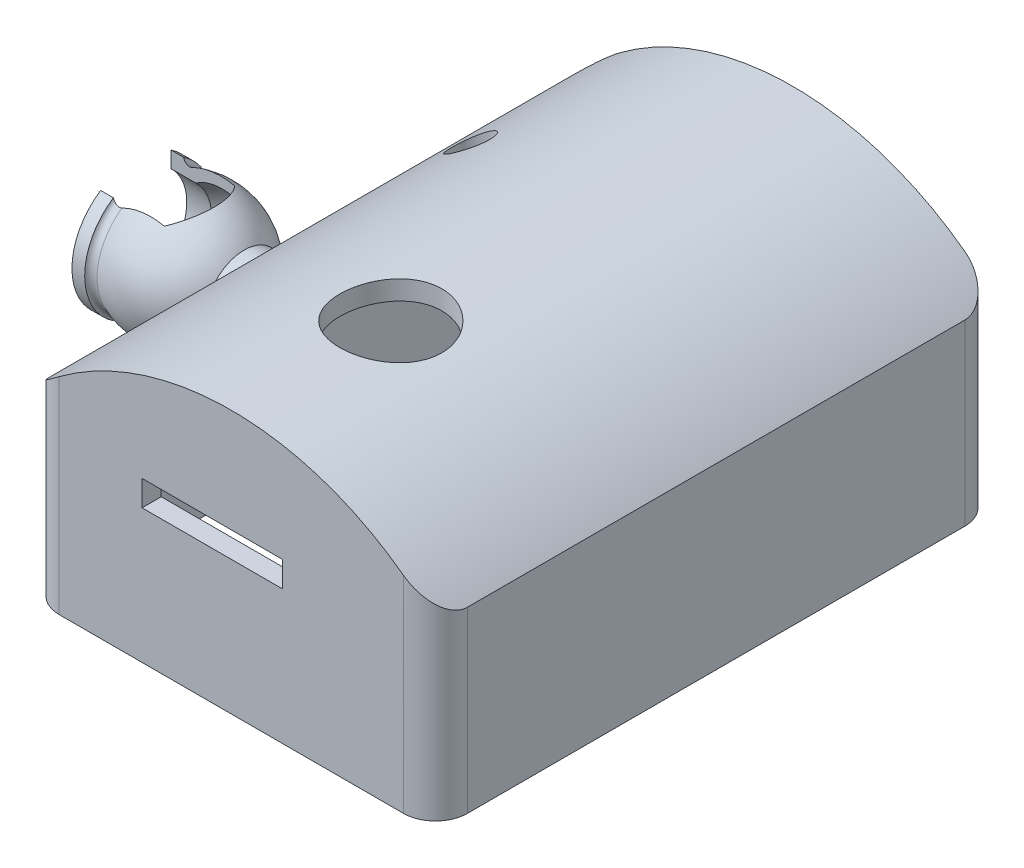
SolidWorks part; units mm, degrees
ref_plane "Front Plane" through (0, 0, 0) normal (0, 0, 1) x (1, 0, 0)
ref_plane "Top Plane" through (0, 0, 0) normal (0, 1, 0) x (1, 0, 0)
ref_plane "Right Plane" through (0, 0, 0) normal (1, 0, 0) x (0, 0, -1)
sketch "Sketch1" plane through (0, 0, 0) normal (0, 0, 1) x (1, 0, 0)
  line L1 (-16, -7) -> (16, -7)
  line L2 (-16, -7) -> (-16, 7)
  line L4 (16, -7) -> (16, 7)
  line L5 (-16, -7) -> (16, 7) construction
  line L6 (-16, 7) -> (16, -7) construction
  arc A0 (-16, 7) -> (16, 7) centre (0, -9) cw
  point P0 (0, 0)
  dimension "D1" = 14
  dimension "D2" = 32
extrude "Boss-Extrude1" add sketch "Sketch1" along normal blind 44
shell "Shell1" thickness 1.5 removed face at (0, -7, 22)
ref_plane "Plane1" through (0, 18, 0) normal (0, -1, 0) x (-1, 0, 0)
sketch "Sketch4" plane through (0, 18, 0) normal (0, -1, 0) x (-1, 0, 0)
  line L0 (-16, -44) -> (16, -44) construction
  line L1 (16, -44) -> (16, 0) construction
  circle A0 centre (0, -31.5) radius 4
  dimension "D1" = 8
  dimension "D3" = 16
  dimension "D2" = 12.5
extrude "Cut-Extrude1" cut sketch "Sketch4" along normal blind 44
ref_plane "Plane2" through (0, 4.5, 0) normal (0, -1, 0) x (-1, 0, 0)
sketch "Sketch6" plane through (0, 4.5, 0) normal (0, -1, 0) x (-1, 0, 0)
  line L0 (-14.5, -1.5) -> (14.5, -1.5) construction
  line L1 (-14.25, -5.5) -> (14.25, -5.5)
  line L2 (-14.25, -5.5) -> (-14.25, -1.5)
  line L3 (-14.25, -1.5) -> (14.25, -1.5)
  line L4 (14.25, -5.5) -> (14.25, -1.5)
  line L5 (-14.25, -5.5) -> (14.25, -1.5) construction
  line L6 (-14.25, -1.5) -> (14.25, -5.5) construction
  line L7 (-14.5, -42.5) -> (-14.5, -1.5) construction
  line L8 (14.5, -42.5) -> (14.5, -1.5) construction
  line L9 (14.5, -42.5) -> (-14.5, -42.5) construction
  line L10 (-14.25, -39.5) -> (-8.5, -39.5)
  line L11 (-14.25, -39.5) -> (-14.25, -42.5)
  line L12 (-14.25, -42.5) -> (-8.5, -42.5)
  line L13 (-8.5, -39.5) -> (-8.5, -42.5)
  line L14 (-14.25, -39.5) -> (-8.5, -42.5) construction
  line L15 (-14.25, -42.5) -> (-8.5, -39.5) construction
  line L16 (14.5, -42.5) -> (14.5, -1.5) construction
  line L17 (8.5, -39.5) -> (14.25, -39.5)
  line L18 (8.5, -39.5) -> (8.5, -42.5)
  line L19 (8.5, -42.5) -> (14.25, -42.5)
  line L20 (14.25, -39.5) -> (14.25, -42.5)
  line L21 (8.5, -39.5) -> (14.25, -42.5) construction
  line L22 (8.5, -42.5) -> (14.25, -39.5) construction
  point P0 (0, -3.5)
  point P7 (-14.25, -3.5)
  point P12 (-11.375, -41)
  point P19 (11.375, -41)
  dimension "D1" = 4
  dimension "D2" = 0.25
  dimension "D3" = 0.25
  dimension "D4" = 3
  dimension "D5" = 0.25
  dimension "D6" = 5.75
  dimension "D7" = 3
  dimension "D8" = 0.25
  dimension "D9" = 5.75
extrude "Boss-Extrude2" add sketch "Sketch6" against normal up to surface (2.0982 mm away) up to face at (0, 9.2468, 22)
sketch "Sketch7" plane through (0, 0, 44) normal (0, 0, 1) x (1, 0, 0)
  line L0 (-16, 7) -> (-16, -7) construction
  line L1 (-7, 3.5) -> (4, 3.5)
  line L2 (-7, 3.5) -> (-7, 5.5)
  line L3 (-7, 5.5) -> (4, 5.5)
  line L4 (4, 3.5) -> (4, 5.5)
  line L5 (-7, 3.5) -> (4, 5.5) construction
  line L6 (-7, 5.5) -> (4, 3.5) construction
  line L7 (-16, -7) -> (16, -7) construction
  point P0 (-1.5, 4.5)
  dimension "D1" = 11
  dimension "D2" = 2
  dimension "D3" = 9
  dimension "D4" = 10.5
extrude "Cut-Extrude2" cut sketch "Sketch7" against normal blind 20
sketch "Sketch8" plane through (0, 4.5, 0) normal (0, -1, 0) x (-1, 0, 0)
  line L0 (14.5, -42.5) -> (14.5, -1.5) construction
  line L1 (16, 0) -> (-16, 0) construction
  circle A0 centre (12.75, -12.5) radius 2.5
  dimension "D1" = 5
  dimension "D2" = 1.75
  dimension "D3" = 12.5
extrude "Boss-Extrude3" add sketch "Sketch8" against normal up to surface (3.3465 mm away) up to face at (0, 7.9628, 26.875)
sketch "Sketch9" plane through (0, 4.5, 0) normal (0, -1, 0) x (-1, 0, 0)
  circle A0 centre (12.75, -12.5) radius 1.5
  dimension "D1" = 3
extrude "Cut-Extrude3" cut sketch "Sketch9" against normal blind 20
sketch "Sketch10" plane through (-16, 0, 0) normal (-1, 0, 0) x (0, 0, 1)
  line L0 (0, 7) -> (44, -7) construction
  circle A0 centre (22, 0) radius 3
  dimension "D1" = 6
extrude "Boss-Extrude4" add sketch "Sketch10" along normal blind 5
sketch "Sketch11" plane through (0, 0, 0) normal (0, 1, 0) x (1, 0, 0)
  line L0 (-21, -22) -> (-29.5, -22) construction
  line L1 (-21, -19) -> (-21, -25) construction
  line L2 (-29.5, -22) -> (-29.5, -28.6326) construction
  line L3 (-28.75, -25.125) -> (-28.75, -24.5)
  line L4 (-28.75, -24.5) -> (-29.5, -24.5)
  line L5 (-29.5, -24.5) -> (-29.5, -27)
  line L6 (-29.5, -27) -> (-28.5, -27)
  line L7 (-28.5, -27) -> (-28.5, -26.375)
  line L8 (-21, -25) -> (-21, -23)
  circle A0 centre (-25.25, -22) radius 4.2668 construction
  arc A1 (-21, -25) -> (-28.5, -26.375) centre (-25.5653, -21.2404) cw
  arc A2 (-28.75, -25.125) -> (-21, -23) centre (-25.474, -21.8778) ccw
  dimension "D1" = 8.5
  dimension "D2" = 0.75
  dimension "D3" = 2.5
  dimension "D4" = 1
  dimension "D5" = 0.625
  dimension "D6" = 0.625
  dimension "D7" = 10
  dimension "D8" = 2
revolve "Revolve1" add sketch "Sketch11" angle 360 about L0
sketch "Sketch12" plane through (0, 0, 0) normal (0, 1, 0) x (1, 0, 0)
  line L0 (-21, -22) -> (-35.1968, -22) construction
  line L1 (-21, -25) -> (-21, -19) construction
  line L2 (-29.5, -19.25) -> (-29.5, -24.75)
  line L3 (-29.5, -17) -> (-29.5, -27) construction
  line L4 (-29.5, -24.75) -> (-24.5, -24.75)
  line L5 (-29.5, -19.25) -> (-24.5, -19.25)
  arc A0 (-24.5, -19.25) -> (-24.5, -24.75) centre (-27.25, -22) cw
  point P9 (-29.5, -22)
  dimension "D1" = 5.5
  dimension "D2" = 5
  dimension "D3" = 5
extrude "Cut-Extrude4" cut sketch "Sketch12" against normal blind 10 and the other way blind 10
sketch "Sketch13" plane through (-29.5, 0, 0) normal (-1, 0, 0) x (0, 0, 1)
  circle A0 centre (22, 0) radius 4
  arc A1 (24.75, -4.1758) -> (24.75, 4.1758) centre (22, 0) ccw construction
  dimension "D1" = 1
extrude "Cut-Extrude5" cut sketch "Sketch13" against normal blind 2
fillet "Fillet1" radius 0.5 2 edges at (-28.5, 0, 17.625) (-28.5, 0, 26.375)
fillet "Fillet2" radius 2.5 8 edges at (14.5, -0.3169, 42.5) (-14.5, -0.3169, 42.5) (-14.5, -0.3169, 1.5) (14.5, -0.3169, 1.5) (16, 0, 0) (16, 0, 44) (-16, 0, 44) (-16, 0, 0)
